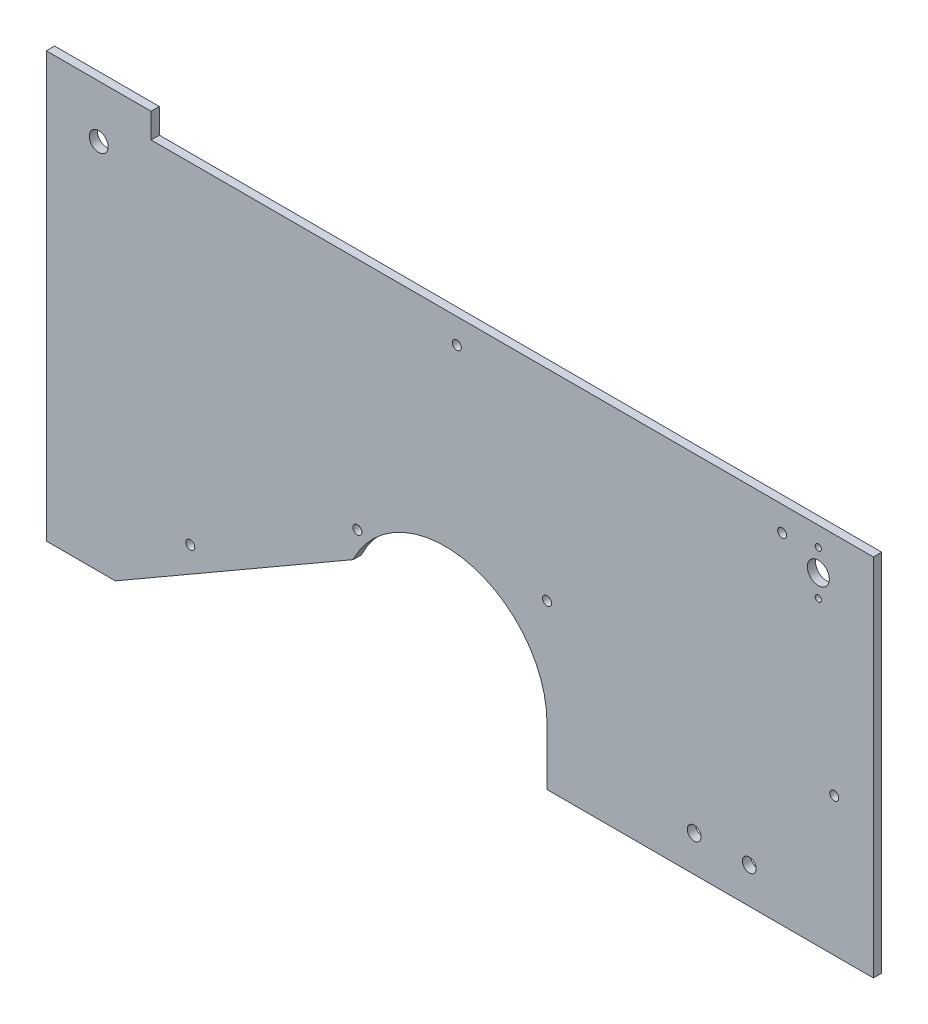
SolidWorks part; units mm, degrees
ref_plane "Front Plane" through (0, 0, 0) normal (0, 0, 1) x (1, 0, 0)
ref_plane "Top Plane" through (0, 0, 0) normal (0, 1, 0) x (1, 0, 0)
ref_plane "Right Plane" through (0, 0, 0) normal (1, 0, 0) x (0, 0, -1)
sketch "Sketch2" plane through (0, 0, 0) normal (0, 0, 1) x (1, 0, 0)
  line L0 (25.0304, 0) -> (111.2865, 49.8)
  line L1 (0, 0) -> (25.0304, 0)
  line L2 (0, 0) -> (0, 154)
  line L4 (300, 0) -> (300, 145)
  line L5 (181.6, 33.7) -> (181.6, 0)
  line L6 (181.6, 0) -> (300, 0)
  line L7 (19, 135) -> (19, 164.3674) construction
  line L11 (38, 145) -> (300, 145)
  line L12 (0, 154) -> (19, 154)
  line L13 (19, 154) -> (38, 154)
  line L14 (38, 154) -> (38, 145)
  line L15 (19, 135) -> (50019, 135) construction
  line L20 (19, 135) -> (19, -49865) construction
  circle A0 centre (19, 135) radius 3.425
  arc A1 (181.6, 33.7) -> (111.2865, 49.8) centre (144.6, 33.7) ccw
  point P19 (19, 154)
  dimension "D3" = 135
  dimension "D4" = 19
  dimension "D5" = 6.85
  dimension "D6" = 74
  dimension "D7" = 155.4
  dimension "D8" = 33.7
  dimension "D1" = 300
  dimension "D2" = 154
  dimension "D9" = 30
  dimension "D10" = 99.6
  dimension "D11" = 19
extrude "Boss-Extrude2" add sketch "Sketch2" along normal blind 3
sketch "Sketch3" plane through (0, 0, 3) normal (0, 0, 1) x (1, 0, 0)
  line L0 (300, 0) -> (300, 145) construction
  line L1 (181.6, 0) -> (300, 0)
  line L2 (181.6, 0) -> (181.6, 12.75)
  line L3 (181.6, 12.75) -> (300, 12.75)
  line L4 (300, 0) -> (300, 12.75)
  dimension "D1" = 12.75
extrude "Cut-Extrude1" cut sketch "Sketch3" against normal through all
sketch "Sketch4" plane through (0, 0, 3) normal (0, 0, 1) x (1, 0, 0)
  line L0 (19, 135) -> (19, -49865) construction
  line L1 (19, 135) -> (-49981, 135) construction
sketch "Sketch5" plane through (0, 0, 3) normal (0, 0, 1) x (1, 0, 0)
  line L0 (300, 12.75) -> (300, 145) construction
  line L1 (300, 12.75) -> (181.6, 12.75) construction
  line L2 (300, 145) -> (38, 145) construction
  line L3 (0, 154) -> (0, 0) construction
  line L4 (0, 0) -> (25.0304, 0) construction
  circle A0 centre (254.98, 25.75) radius 2.5
  circle A1 centre (234.98, 25.75) radius 2.5
  circle A2 centre (280, 130) radius 4
  circle A3 centre (280, 138) radius 1.125
  circle A4 centre (280, 122) radius 1.125
  circle A5 centre (181.6, 72.03) radius 1.625
  circle A6 centre (285.78, 62.92) radius 1.625
  circle A7 centre (52.23, 24.91) radius 1.625
  circle A8 centre (112.84, 59.93) radius 1.625
  circle A9 centre (266.89, 135.99) radius 1.625
  circle A10 centre (148.89, 135.99) radius 1.625
  dimension "D1" = 5
  dimension "D2" = 45.02
  dimension "D3" = 13
  dimension "D4" = 5
  dimension "D5" = 20
  dimension "D6" = 13
  dimension "D9" = 8
  dimension "D10" = 2.25
  dimension "D11" = 8
  dimension "D12" = 20
  dimension "D13" = 8
  dimension "D14" = 20
  dimension "D15" = 2.25
  dimension "D16" = 3.25
  dimension "D17" = 118.4
  dimension "D18" = 72.97
  dimension "D19" = 3.25
  dimension "D20" = 14.22
  dimension "D21" = 82.08
  dimension "D22" = 52.23
  dimension "D23" = 3.25
  dimension "D24" = 24.91
  dimension "D25" = 112.84
  dimension "D26" = 3.25
  dimension "D27" = 59.93
  dimension "D28" = 9.01
  dimension "D29" = 3.25
  dimension "D30" = 33.11
  dimension "D31" = 3.25
  dimension "D32" = 9.01
  dimension "D33" = 118
  dimension "D7" = 20
  dimension "D8" = 15
extrude "Cut-Extrude2" cut sketch "Sketch5" against normal through all
